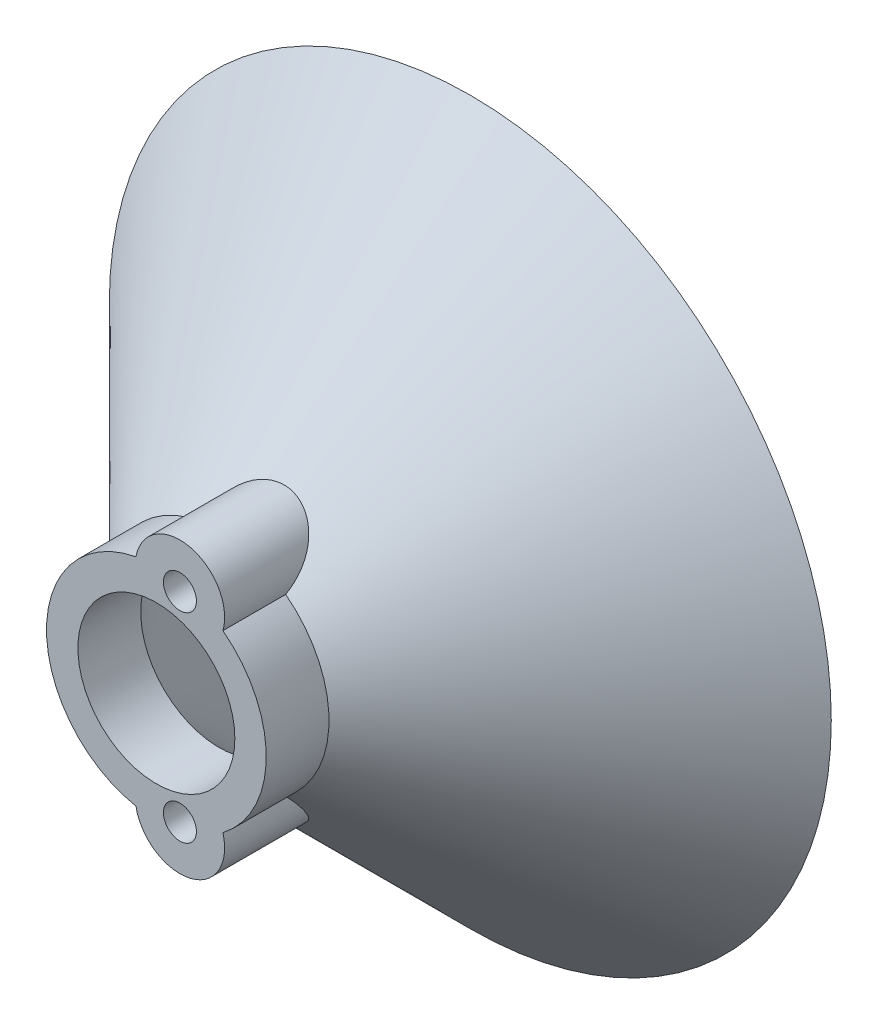
SolidWorks part; units mm, degrees
ref_plane "Спереди" through (0, 0, 0) normal (0, 0, 1) x (1, 0, 0)
ref_plane "Сверху" through (0, 0, 0) normal (0, 1, 0) x (1, 0, 0)
ref_plane "Справа" through (0, 0, 0) normal (1, 0, 0) x (0, 0, -1)
other "Configuration Table"
sketch "Эскиз1" plane through (0, 0, 0) normal (0, 0, 1) x (1, 0, 0)
  line L0 (0, 0) -> (1.5, 0) construction
  line L1 (1.5, 0) -> (1.5, 6.36) construction
  line L2 (1.5, 0) -> (1.5, -6.36) construction
  circle A0 centre (0, 0) radius 5
  circle A2 centre (0, 0) radius 7
  circle A3 centre (1.5, 6.36) radius 1.05
  circle A4 centre (1.5, -6.36) radius 1.05
  circle A5 centre (1.5, 6.36) radius 2.85
  circle A6 centre (1.5, -6.36) radius 2.85
  dimension "D1" = 10
  dimension "D2" = 2
  dimension "D6" = 2.1
  dimension "D7" = 1.8
  dimension "D3" = 1.5
  dimension "D4" = 6.36
  dimension "D5" = 6.36
extrude "Бобышка-Вытянуть1" add sketch "Эскиз1" along normal blind 4 contours A6 A0 A5 A2 | A6 A2 A5 A0 | A2 A5 A0 A3 | A2 A6 A0 A4 | A2 A6 A4 | A2 A5 A3 region at (5.2745, 0, 0) region at (1.1624, 4.9284, 0) region at (3.7365, -4.698, 0) region at (-5.1503, 0, 0) region at (1.8212, 7.7219, 0) region at (1.8212, -7.7219, 0)
sketch "Эскиз2" plane through (0, 0, 0) normal (0, 0, -1) x (-1, 0, 0)
  circle A2 centre (0, 0) radius 7
extrude "Бобышка-Вытянуть2" add sketch "Эскиз2" along normal blind 16 draft 45 draft outward yes
sketch "Эскиз3" plane through (0, 0, 0) normal (0, 0, 1) x (1, 0, 0)
  circle A1 centre (0, 0) radius 5
  circle A2 centre (0, 0) radius 5
  dimension "D1" = 0
extrude "Вырез-Вытянуть1" cut sketch "Эскиз3" against normal through all draft 45 draft outward yes
sketch "Эскиз4" plane through (0, 0, 0) normal (0, 0, -1) x (-1, 0, 0)
  arc A4 (-4.2386, -5.5709) -> (-2.5371, -6.524) centre (0, 0) ccw
  arc A5 (-4.2386, -5.5709) -> (1.3026, -6.8777) centre (-1.5, -6.36) ccw
  arc A6 (-0.6455, -6.9702) -> (1.3026, -6.8777) centre (0, 0) ccw
  arc A7 (-2.5371, -6.524) -> (-0.6455, -6.9702) centre (-1.5, -6.36) ccw
  arc A8 (-4.2386, -5.5709) -> (-2.5371, -6.524) centre (0, 0) ccw
  arc A9 (-4.2386, -5.5709) -> (1.3026, -6.8777) centre (-1.5, -6.36) ccw
  arc A10 (-0.6455, -6.9702) -> (1.3026, -6.8777) centre (0, 0) ccw
  arc A11 (-2.5371, -6.524) -> (-0.6455, -6.9702) centre (-1.5, -6.36) ccw
  arc A12 (1.3026, 6.8777) -> (-0.6455, 6.9702) centre (0, 0) ccw
  arc A13 (1.3026, 6.8777) -> (-4.2386, 5.5709) centre (-1.5, 6.36) ccw
  arc A14 (-2.5371, 6.524) -> (-4.2386, 5.5709) centre (0, 0) ccw
  arc A15 (-0.6455, 6.9702) -> (-2.5371, 6.524) centre (-1.5, 6.36) ccw
  arc A16 (1.3026, 6.8777) -> (-0.6455, 6.9702) centre (0, 0) ccw
  arc A17 (1.3026, 6.8777) -> (-4.2386, 5.5709) centre (-1.5, 6.36) ccw
  arc A18 (-2.5371, 6.524) -> (-4.2386, 5.5709) centre (0, 0) ccw
  arc A19 (-0.6455, 6.9702) -> (-2.5371, 6.524) centre (-1.5, 6.36) ccw
  dimension "D1" = 0
  dimension "D2" = 0
extrude "Бобышка-Вытянуть3" add sketch "Эскиз4" along normal up to next
sketch "Эскиз5" plane through (0, 0, 0) normal (0, 0, 1) x (1, 0, 0)
  circle A14 centre (1.5, 6.36) radius 1.05 construction
  circle A15 centre (1.5, 6.36) radius 1.05
  circle A16 centre (1.5, -6.36) radius 1.05 construction
  circle A17 centre (1.5, -6.36) radius 1.05
extrude "Бобышка-Вытянуть5" add sketch "Эскиз5" against normal up to body
